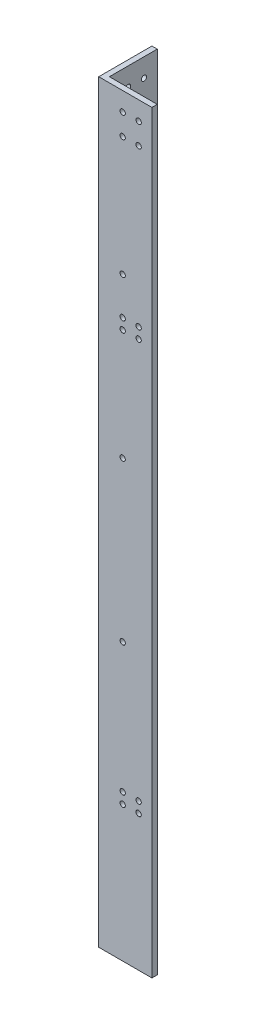
SolidWorks part; units mm, degrees
ref_plane "Front Plane" through (0, 0, 0) normal (0, 0, 1) x (1, 0, 0)
ref_plane "Top Plane" through (0, 0, 0) normal (0, 1, 0) x (1, 0, 0)
ref_plane "Right Plane" through (0, 0, 0) normal (1, 0, 0) x (0, 0, -1)
sketch "Sketch2" plane through (0, 0, 0) normal (0, 1, 0) x (1, 0, 0)
  line L0 (0, 31.75) -> (3.175, 31.75)
  line L1 (3.175, 31.75) -> (3.175, 3.175)
  line L2 (3.175, 3.175) -> (31.75, 3.175)
  line L3 (31.75, 3.175) -> (31.75, 0)
  line L4 (31.75, 0) -> (0, 0)
  line L5 (0, 0) -> (0, 31.75)
  point P9 (1.5875, 31.75)
  point P10 (31.75, 1.5875)
  dimension "D4" = 3.175
  dimension "D1" = 31.75
  dimension "D2" = 31.75
  dimension "D3" = 3.175
extrude "Boss-Extrude1" add sketch "Sketch2" along normal blind 450
sketch "BackSideHoles-Sketch3" plane through (0, 0, 0) normal (0, 0, 1) x (1, 0, 0)
  line L0 (0, 0) -> (31.75, 0) construction
  line L3 (0, 450) -> (0, 0) construction
  circle A0 centre (14.2875, 81.1125) radius 1.5875
  circle A1 centre (23.8125, 81.1125) radius 1.5875
  circle A2 centre (14.2875, 87.4625) radius 1.5875
  circle A3 centre (23.8125, 87.4625) radius 1.5875
  circle A4 centre (14.2875, 438.8875) radius 1.5875
  circle A5 centre (14.2875, 426.1875) radius 1.5875
  circle A6 centre (23.8125, 438.8875) radius 1.5875
  circle A7 centre (23.8125, 426.1875) radius 1.5875
  circle A10 centre (14.2875, 332.6026) radius 1.5875
  circle A11 centre (23.8125, 332.6026) radius 1.5875
  circle A12 centre (14.2875, 326.2526) radius 1.5875
  circle A13 centre (23.8125, 326.2526) radius 1.5875
  circle A14 centre (14.2875, 165) radius 1.5875
  circle A15 centre (14.2875, 260) radius 1.5875
  circle A16 centre (14.2875, 355) radius 1.5875
  dimension "D4" = 3.175
  dimension "D1" = 81.1125
  dimension "D2" = 14.2875
  dimension "D8" = 11.1125
  dimension "D5" = 6.35
  dimension "D7" = 6.35
  dimension "D9" = 12.7
  dimension "D3" = 9.525
  dimension "D10" = 332.6026
  dimension "D11" = 165
  dimension "D12" = 95
  dimension "D13" = 95
sketch "RightSideHoles-Sketch4" plane through (0, 0, 0) normal (-1, 0, 0) x (0, 0, 1)
  line L0 (-31.75, 450) -> (0, 450) construction
  line L1 (0, 450) -> (0, 0) construction
  line L3 (-31.75, 0) -> (0, 0) construction
  circle A0 centre (-23.8125, 81.1125) radius 1.5875
  circle A1 centre (-14.2875, 81.1125) radius 1.5875
  circle A2 centre (-23.8125, 87.4625) radius 1.5875
  circle A3 centre (-14.2875, 87.4625) radius 1.5875
  circle A4 centre (-23.8125, 438.8875) radius 1.5875
  circle A5 centre (-14.2875, 438.8875) radius 1.5875
  circle A6 centre (-23.8125, 426.1875) radius 1.5875
  circle A7 centre (-14.2875, 426.1875) radius 1.5875
  circle A10 centre (-23.8125, 332.6026) radius 1.5875
  circle A11 centre (-14.2875, 332.6026) radius 1.5875
  circle A12 centre (-23.8125, 319.9026) radius 1.5875
  circle A13 centre (-14.2875, 319.9026) radius 1.5875
  circle A14 centre (-23.8125, 7.9375) radius 1.5875
  circle A15 centre (-14.2875, 7.9375) radius 1.5875
  circle A16 centre (-14.2875, 165) radius 1.5875
  circle A17 centre (-14.2875, 260) radius 1.5875
  circle A18 centre (-14.2875, 355) radius 1.5875
  dimension "D4" = 3.175
  dimension "D2" = 14.2875
  dimension "D5" = 6.35
  dimension "D9" = 12.7
  dimension "D10" = 332.6026
  dimension "D13" = 95
  dimension "D3" = 81.1125
  dimension "D6" = 11.1125
  dimension "D8" = 7.9375
  dimension "D7" = 12.7
  dimension "D11" = 9.525
  dimension "D12" = 165
  dimension "D14" = 95
extrude "BackSideHoles-Cut-Extrude1" cut sketch "BackSideHoles-Sketch3" against normal blind 3.175
extrude "RightSideHoles-Cut-Extrude2" cut sketch "RightSideHoles-Sketch4" against normal blind 3.175
equation "\"RailThickness\"= .125in'Spec"
equation "\"VSWidth\"= 1.25in'Spec"
equation "\"VSHeight\"= 1.25in'Spec"
equation "\"VSLength\"= 450mm"
equation "\"HoleOffsetFromEdge\"= \"RailThickness\" * 2.5"
equation "\"HoleOffsetFromSide\"= \"RailThickness\" * 3.5"
equation "\"LegHeight\"= 70mm'Space needed for PSU/Stepper/Electronics"
equation "\"VSBottomSideRailHoleY1FromBottomOfLowerRail\"= \"V1 BottomOfLowerRail\" + \"HoleOffsetFromSide\"'Equals 70.1125"
equation "\"VSSideRailHoleX1FromSide\"= \"HoleOffsetFromSide\" + \"RailThickness\""
equation "\"FasteningHoleDiameter\"= .125in"
equation "\"VSBottomSideRailHoleY2FromY1\"= \"LowerRailHeight\" - \"HoleOffsetFromSide\" - \"HoleOffsetFromEdge\"'Equals 6.35"
equation "\"VSTopSideRailHoleY1FromEdge\"= \"HoleOffsetFromEdge\" + \"RailThickness\""
equation "\"D4@BackSideHoles-Sketch3\" = \"FasteningHoleDiameter\""
equation "\"D1@BackSideHoles-Sketch3\" = \"VSBottomSideRailHoleY1FromBottomOfLowerRail\""
equation "\"D2@BackSideHoles-Sketch3\" = \"VSSideRailHoleX1FromSide\""
equation "\"D1@Boss-Extrude1\"=\"VSLength\""
equation "\"D4@RightSideHoles-Sketch4\"=\"FasteningHoleDiameter\""
equation "\"D3@RightSideHoles-Sketch4\" = \"VSBottomSideRailHoleY1FromBottomOfLowerRail\""
equation "\"D2@RightSideHoles-Sketch4\"=\"VSSideRailHoleX1FromSide\""
equation "\"D8@BackSideHoles-Sketch3\" = \"VSTopSideRailHoleY1FromEdge\""
equation "\"D6@RightSideHoles-Sketch4\"=\"VSTopSideRailHoleY1FromEdge\""
equation "\"VSMidSideRailHoleY1FromV8TopOfMidSideRail\"= \"V8 ToTopOfMidSideRail\" - \"HoleOffsetFromEdge\"'Equals 308.2875"
equation "\"LowerRailHeight\"= 1.00in"
equation "\"D2@Sketch2\"=\"VSWidth\""
equation "\"D1@Sketch2\"=\"VSHeight\""
equation "\"MidBackRailHeight\"= 1.00in"
equation "\"VSMidBackRailHoleY1FromV7TopOfMidBackRail\"= \"V7 ToTopOfMidBackRail\" - \"HoleOffsetFromSide\"'Equals 308.2875"
equation "\"TopRailHeight\"= 1.25in"
equation "\"MidSideRailHeight\"= 1.25in"
equation "\"D8@RightSideHoles-Sketch4\"=\"HoleOffsetFromEdge\""
equation "\"D5@BackSideHoles-Sketch3\"=\"VSBottomSideRailHoleY2FromY1\""
equation "\"D5@RightSideHoles-Sketch4\"=\"VSBottomSideRailHoleY2FromY1\""
equation "\"VSMidBackRailHoleY2FromY1\"= \"MidBackRailHeight\" - \"HoleOffsetFromSide\" - \"HoleOffsetFromEdge\"'Equals 6.35"
equation "\"VSMidSideRailHoleY2FromY1\"= \"MidSideRailHeight\" - \"HoleOffsetFromSide\" - \"HoleOffsetFromEdge\"'Equals 12.7"
equation "\"D7@BackSideHoles-Sketch3\"=\"VSMidBackRailHoleY2FromY1\""
equation "\"D9@RightSideHoles-Sketch4\"=\"VSMidSideRailHoleY2FromY1\""
equation "\"VSTopSideRailHoleY2FromY1\"= \"TopRailHeight\" - \"VSTopSideRailHoleY1FromEdge\" - \"HoleOffsetFromEdge\"'Equals 12.7"
equation "\"D9@BackSideHoles-Sketch3\"=\"VSTopSideRailHoleY2FromY1\""
equation "\"VSSideRailHoleX2FromX1\"= \"VSWidth\" - \"VSSideRailHoleX1FromSide\" - \"HoleOffsetFromEdge\""
equation "\"D3@BackSideHoles-Sketch3\"=\"VSSideRailHoleX2FromX1\""
equation "\"D7@RightSideHoles-Sketch4\"=\"VSTopSideRailHoleY2FromY1\""
equation "\"D11@RightSideHoles-Sketch4\"=\"VSSideRailHoleX2FromX1\""
equation "\"V1 BottomOfLowerRail\"= \"LegHeight\""
equation "\"StepperShaftLength\"= 24mm'Pulley will be attached to the end"
equation "\"ZAxisLeadScrewLength\"= 200mm"
equation "\"HotEndToTopOfXAxisGB\"= 63.315144mm'Measured from the100.Should be 63.315144"
equation "\"TopOfGBToBottomOfLinearRail\"= \"LinearGBWidth\" / 2 + \"LinearRailWidth\" / 2"
equation "\"LinearGBWidth\"= 27mm'Spec"
equation "\"V5 ToBottomOfXAxisLinearRail\"= \"V4 ToTopOfBuildPlate/HotEndTip\" + \"HotEndToTopOfXAxisGB\" - \"TopOfGBToBottomOfLinearRail\""
equation "\"LinearRailWidth\"= 12mm'Spec"
equation "\"V6 ToBottomOfGantryPulley\"= \"V5 ToBottomOfXAxisLinearRail\" - \"DistanceFromGABTopToLowerPulley\""
equation "\"GABUpperHeight\"= 6mm"
equation "\"GABMidWallHeight\"= 28mm'Must equal 28 or changes alignment"
equation "\"20TGT2PulleyWidth\"= 8.7mm'The STL of the Pulley in the diagram is a bit larger"
equation "\"GABMidShortRiserHeight\"= \"GABMidWallHeight\" / 2 - \"20TGT2PulleyWidth\"'Equals 5.3"
equation "\"GABRiserBossOffset\"= 0.8mm'Aligns Pulleys"
equation "\"DistanceFromGABTopToLowerPulley\"= \"GABUpperHeight\" + \"GABMidWallHeight\" - \"GABMidShortRiserHeight\" + \"GABRiserBossOffset\" / 2"
equation "\"V7 ToTopOfMidBackRail\"= \"V6 ToBottomOfGantryPulley\" + \"StepperShaftLength\""
equation "\"D10@BackSideHoles-Sketch3\" = \"VSMidBackRailHoleY1FromV7TopOfMidBackRail\""
equation "\"D10@RightSideHoles-Sketch4\"=\"VSMidSideRailHoleY1FromV8TopOfMidSideRail\""
equation "\"BedToBuildPlateStandoffLength\"= 15mm"
equation "\"BuildPlateHeight\"= 8mm'Spec"
equation "\"V4 ToTopOfBuildPlate/HotEndTip\"= \"V2 ToBedAtTopOfZAxis\" + \"BedToBuildPlateStandoffLength\" + \"BuildPlateHeight\""
equation "\"V2 ToBedAtTopOfZAxis\"= \"V1 BottomOfLowerRail\" + \"StepperShaftLength\" + \"ZAxisLeadScrewLength\" - \"LM8UUHeight\" / 2"
equation "\"LM8UUHeight\"= 24mm'Spec"
equation "\"V8 ToTopOfMidSideRail\"= \"V7 ToTopOfMidBackRail\" - \"RailThickness\""
equation "\"VSEnclosureOffsets\"= ( \"VSLength\" - \"LegHeight\" ) / 4"
equation "\"D11@BackSideHoles-Sketch3\"=\"LegHeight\" + \"VSEnclosureOffsets\""
equation "\"D12@BackSideHoles-Sketch3\"=\"VSEnclosureOffsets\""
equation "\"D13@BackSideHoles-Sketch3\"=\"VSEnclosureOffsets\""
equation "\"D12@RightSideHoles-Sketch4\"=\"LegHeight\" + \"VSEnclosureOffsets\""
equation "\"D13@RightSideHoles-Sketch4\"=\"VSEnclosureOffsets\""
equation "\"D14@RightSideHoles-Sketch4\"=\"VSEnclosureOffsets\""
